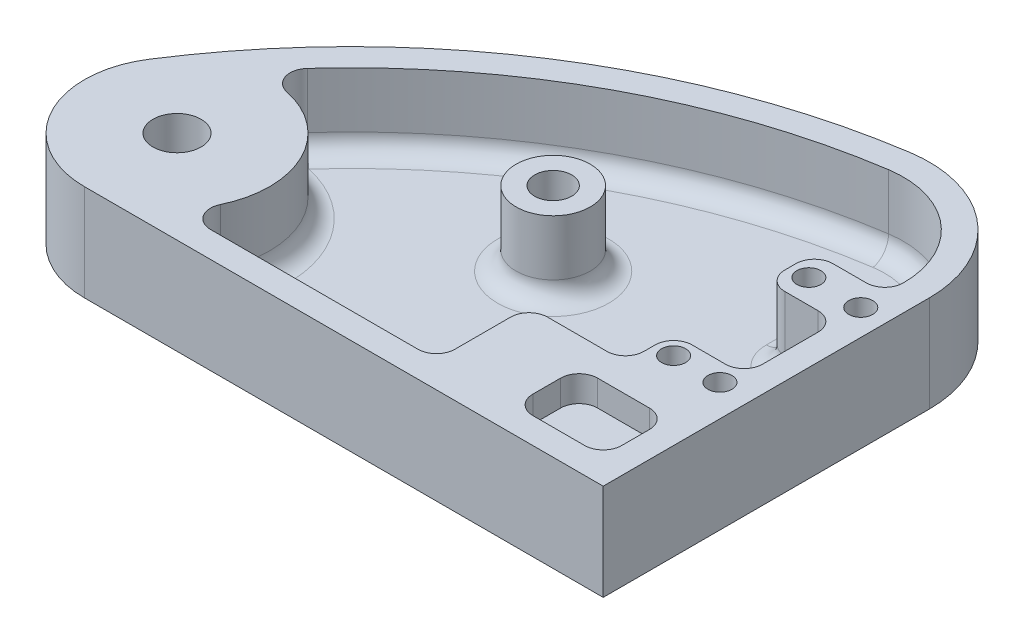
SolidWorks part; units mm, degrees
ref_plane "Front Plane" through (0, 0, 0) normal (0, 0, 1) x (1, 0, 0)
ref_plane "Top Plane" through (0, 0, 0) normal (0, 1, 0) x (1, 0, 0)
ref_plane "Right Plane" through (0, 0, 0) normal (1, 0, 0) x (0, 0, -1)
sketch "Sketch1" plane through (0, 0, 0) normal (0, 1, 0) x (1, 0, 0)
  line L0 (-63, -18.5) -> (-63, -58.5) construction
  line L1 (-63, -63.5) -> (77, -63.5)
  line L2 (77, -63.5) -> (77, 24.5)
  line L3 (-35.963, -56.5) -> (20, -56.5)
  line L4 (25, -51.5) -> (25, -36.5)
  line L5 (30, -31.5) -> (46, -31.5)
  line L6 (51, -26.5) -> (51, -23.5)
  line L7 (56, -18.5) -> (65, -18.5)
  line L8 (70, -13.5) -> (70, 1.5)
  line L9 (65, 6.5) -> (56, 6.5)
  line L10 (51, 11.5) -> (51, 14.5)
  line L11 (56, 19.5) -> (65, 19.5)
  line L12 (25, -51.5) -> (25, -31.5) construction
  line L13 (51, -56.5) -> (65, -56.5)
  line L14 (46, -51.5) -> (46, -44)
  line L15 (51, -39) -> (65, -39)
  line L16 (70, -51.5) -> (70, -44)
  line L17 (25, -31.5) -> (46, -31.5) construction
  line L18 (-45.6506, -56.5) -> (20, -56.5) construction
  line L25 (-45.6506, -49.5) -> (18, -49.5) construction
  line L26 (18, -49.5) -> (18, -24.5) construction
  line L27 (18, -24.5) -> (44, -24.5) construction
  line L28 (44, -24.5) -> (44, -23.5) construction
  line L29 (56, -11.5) -> (63, -11.5) construction
  line L30 (63, -11.5) -> (63, -0.5) construction
  line L31 (63, -0.5) -> (56, -0.5) construction
  line L32 (44, 11.5) -> (44, 14.5) construction
  line L33 (58.3368, 26.2703) -> (69.4897, 19.5) construction
  line L34 (56, 19.5) -> (73.0446, 9.1532) construction
  circle A0 centre (0, 0) radius 5
  circle A1 centre (0, 0) radius 10
  circle A2 centre (-63, -38.5) radius 6.5
  arc A3 (-84.0557, -25.0219) -> (-63, -63.5) centre (-63, -38.5) ccw
  arc A4 (51, 14.5) -> (56, 19.5) centre (56, 14.5) cw
  arc A5 (56, 6.5) -> (51, 11.5) centre (56, 11.5) cw
  arc A6 (70, 1.5) -> (65, 6.5) centre (65, 1.5) ccw
  arc A7 (65, -18.5) -> (70, -13.5) centre (65, -13.5) ccw
  arc A8 (51, -23.5) -> (56, -18.5) centre (56, -23.5) cw
  arc A9 (46, -31.5) -> (51, -26.5) centre (46, -26.5) ccw
  arc A10 (20, -56.5) -> (25, -51.5) centre (20, -51.5) ccw
  arc A11 (51, -56.5) -> (46, -51.5) centre (51, -51.5) cw
  arc A12 (65, -56.5) -> (70, -51.5) centre (65, -51.5) ccw
  arc A13 (65, -39) -> (70, -44) centre (65, -44) cw
  arc A14 (46, -44) -> (51, -39) centre (51, -44) cw
  circle A15 centre (56, -23.5) radius 3.25
  circle A16 centre (68.5, -23.5) radius 3.25
  arc A19 (77, 24.5) -> (40.4751, 55.8889) centre (45.25, 24.5) ccw
  arc A20 (40.4751, 55.8889) -> (-84.0557, -25.0219) centre (67.5453, -122.0639) ccw
  circle A21 centre (56, 13) radius 3.25
  arc A22 (73.0446, 9.1532) -> (40.4751, 55.8889) centre (45.25, 24.5) ccw construction
  circle A23 centre (70, 13) radius 3.25
  arc A24 (51, 14.5) -> (56, 19.5) centre (56, 14.5) cw construction
  arc A25 (69.4897, 19.5) -> (41.5279, 48.9685) centre (45.25, 24.5) ccw construction
  arc A26 (65, 19.5) -> (70, 24.5) centre (65, 24.5) ccw
  arc A27 (25, -36.5) -> (30, -31.5) centre (30, -36.5) cw
  arc A28 (70, 24.5) -> (41.5279, 48.9685) centre (45.25, 24.5) ccw
  arc A29 (41.5279, 48.9685) -> (-60.543, -5.7782) centre (67.5453, -122.0639) ccw
  arc A30 (18, -49.5) -> (18, -49.5) centre (18, -49.5) ccw construction
  arc A31 (44, -23.5) -> (56, -11.5) centre (56, -23.5) cw construction
  arc A32 (44, -24.5) -> (44, -24.5) centre (44, -24.5) ccw construction
  arc A33 (63, -11.5) -> (63, -11.5) centre (63, -11.5) ccw construction
  arc A34 (63, -0.5) -> (63, -0.5) centre (63, -0.5) ccw construction
  arc A35 (56, -0.5) -> (44, 11.5) centre (56, 11.5) cw construction
  arc A36 (44, 14.5) -> (58.3368, 26.2703) centre (56, 14.5) cw construction
  arc A37 (41.5279, 48.9685) -> (-78.1601, -28.7958) centre (67.5453, -122.0639) ccw construction
  arc A38 (-40.4692, -49.3333) -> (-57.8676, -14.0325) centre (-63, -38.5) ccw
  arc A39 (-35.963, -56.5) -> (-40.4692, -49.3333) centre (-35.963, -51.5) cw
  arc A40 (-60.543, -5.7782) -> (-57.8676, -14.0325) centre (-56.8411, -9.139) ccw
  point P45 (70, -18.5)
  point P52 (25, -56.5)
  point P55 (46, -56.5)
  point P58 (70, -56.5)
  point P61 (70, -39)
  point P92 (69.5169, 19.6336)
  point P93 (69.4909, 19.5)
  point P94 (51, 13)
  point P95 (0, 0)
  point P103 (25, -31.5)
  point P104 (-63, -18.5)
  point P108 (-45.6506, -56.5)
  dimension "D1" = 20
  dimension "D2" = 10
  dimension "D3" = 50
  dimension "D4" = 13
  dimension "D15" = 5
  dimension "D16" = 5
  dimension "D19" = 6.5
  dimension "D22" = 31.75
  dimension "D23" = 180
  dimension "D24" = 7
  dimension "D25" = 5
  dimension "D26" = 5
  dimension "D27" = 5
  dimension "D5" = 24
  dimension "D6" = 17.5
  dimension "D7" = 7
  dimension "D8" = 7
  dimension "D9" = 140
  dimension "D10" = 25
  dimension "D11" = 63.5
  dimension "D12" = 13
  dimension "D13" = 45
  dimension "D14" = 25
  dimension "D17" = 25
  dimension "D18" = 13
  dimension "D20" = 12.5
  dimension "D21" = 88
extrude "Boss-Extrude1" add sketch "Sketch1" along normal blind 26 contours A19 A20 A3 L1 L2 A40 A29 A28 A26 L11 A4 L10 A5 L9 A6 L8 A7 L7 A8 L6 A9 L5 A27 L4 A10 L3 A39 A38 A23 A21 L14 A14 L15 A13 L16 A12 L13 A11 A2 A15 A16 | A1 A0 region at (-83.1427, 0, 49.5223) region at (-9.7172, 0, 0)
extrude "Boss-Extrude2" add sketch "Sketch1<3>" along normal blind 19 contours A14 L14 A11 L13 A12 L16 A13 L15 region at (58, 0, 47.75)
sketch "Sketch1<3>" plane through (0, 0, 0) normal (0, 1, 0) x (1, 0, 0) same geometry as "Sketch1"
extrude "Boss-Extrude3" add sketch "Sketch1<4>" along normal blind 6 contours A29 A40 A38 A39 L3 A10 L4 A27 L5 A9 L6 A8 L7 A7 L8 A6 L9 A5 L10 A4 L11 A26 A28 A1 region at (8.91, 0, 4.5856)
sketch "Sketch1<4>" plane through (0, 0, 0) normal (0, 1, 0) x (1, 0, 0) same geometry as "Sketch1"
fillet "Fillet1" radius 5 24 edges at (-40.1958, 6, 54.1615) (-40.5757, 6, 27.4479) (-61.5975, 6, 10.6807) (-14.2254, 6, -30.3912) (61.3813, 6, -43.2708) (68.5355, 6, -20.9645) (60.5, 6, -19.5) (52.4645, 6, -18.0355) (51, 6, -13) (52.4645, 6, -7.9645) (60.5, 6, -6.5) (68.5355, 6, -5.0355) (70, 6, 6) (68.5355, 6, 17.0355) (60.5, 6, 18.5) (52.4645, 6, 19.9645) (51, 6, 25) (49.5355, 6, 30.0355) (38, 6, 31.5) (26.4645, 6, 32.9645) (25, 6, 44) (23.5355, 6, 55.0355) (-7.9815, 6, 56.5) (0, 6, 10)
